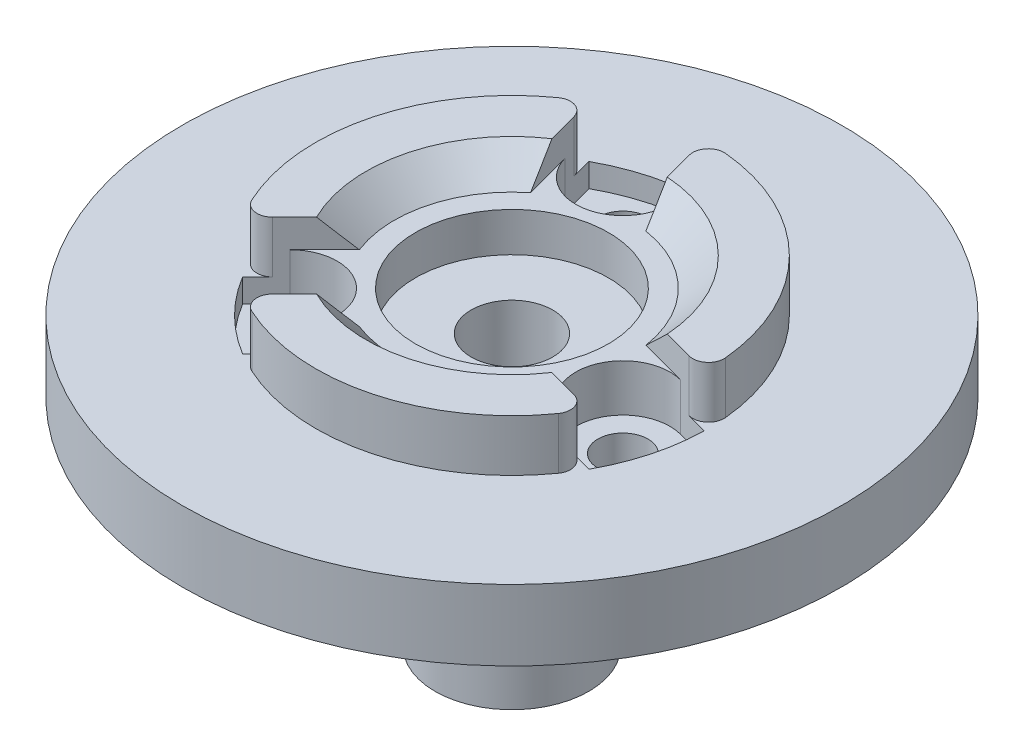
SolidWorks part; units mm, degrees
material "CA"
ref_plane "前视基准面" through (0, 0, 0) normal (0, 0, 1) x (1, 0, 0)
ref_plane "上视基准面" through (0, 0, 0) normal (0, 1, 0) x (1, 0, 0)
ref_plane "右视基准面" through (0, 0, 0) normal (1, 0, 0) x (0, 0, -1)
sketch "草图1" plane through (0, 0, 0) normal (0, 1, 0) x (1, 0, 0)
  circle A0 centre (0, 0) radius 4
  circle A1 centre (0, 0) radius 2.625
  dimension "D1" = 8
  dimension "D2" = 5.25
extrude "凸台-拉伸1" add sketch "草图1" along normal blind 6
sketch "草图2" plane through (0, 0, 0) normal (0, -1, 0) x (-1, 0, 0)
  circle A0 centre (0, 0) radius 12.5
  circle A1 centre (0, 0) radius 4 construction
  circle A2 centre (0, 0) radius 2.6
  dimension "D1" = 25
  dimension "D2" = 5.2
extrude "凸台-拉伸2" add sketch "草图2" against normal blind 6
sketch "草图3" plane through (0, 6, 0) normal (0, 1, 0) x (1, 0, 0)
  line L0 (-2.5882, 9.6593) -> (0, 0) construction
  line L1 (0, 0) -> (0, 2.7054) construction
  circle A0 centre (-2.5882, 9.6593) radius 1.6
  dimension "D1" = 3.2
  dimension "D2" = 10
  dimension "D3" = 15
extrude "切除-拉伸1" cut sketch "草图3" against normal blind 15
sketch "草图6" plane through (0, 6, 0) normal (0, 1, 0) x (1, 0, 0)
  line L0 (-6.0385, 10.9447) -> (-5.486, 8.8828)
  line L1 (0.3096, 10.4357) -> (-0.2429, 12.4976)
  line L2 (-2.5882, 9.6593) -> (0, 0) construction
  circle A0 centre (-2.5882, 9.6593) radius 1.6
  circle A1 centre (-2.5882, 9.6593) radius 3
  circle A2 centre (0, 0) radius 12.5
  circle A3 centre (0, 0) radius 12.5 construction
  circle A6 centre (-2.5882, 9.6593) radius 1.6 construction
  dimension "D1" = 3.2
  dimension "D2" = 6
extrude "切除-拉伸5" cut sketch "草图6" against normal blind 3
pattern_circular "阵列(圆周)1" count 3 over 360 about axis through (0, 0, 0) along (0, 1, 0) of "切除-拉伸1", "切除-拉伸5"
sketch "草图4" plane through (0, 0, 0) normal (0, -1, 0) x (-1, 0, 0)
  circle A0 centre (0, 0) radius 2.6
  circle A1 centre (0, 0) radius 4.9
  dimension "D1" = 9.8
  dimension "D2" = 5.2
extrude "凸台-拉伸3" add sketch "草图4" along normal blind 13.8
sketch "草图7" plane through (0, 6, 0) normal (0, 1, 0) x (1, 0, 0)
  circle A0 centre (0, 0) radius 6.15
  circle A2 centre (0, 0) radius 2.6 construction
  dimension "D1" = 12.3
extrude "切除-拉伸7" cut sketch "草图7" against normal blind 2.5
sketch "草图8" plane through (0, -13.8, 0) normal (0, -1, 0) x (-1, 0, 0)
  line L0 (0, 0) -> (-9.6593, -2.5882) construction
  line L1 (-2.572, -2.572) -> (0.9414, -3.5134)
  line L2 (0.9414, -3.5134) -> (3.5134, -0.9414)
  line L3 (3.5134, -0.9414) -> (2.572, 2.572)
  line L4 (2.572, 2.572) -> (-0.9414, 3.5134)
  line L5 (-0.9414, 3.5134) -> (-3.5134, 0.9414)
  line L6 (-3.5134, 0.9414) -> (-2.572, -2.572)
  circle A0 centre (0, 0) radius 3.15 construction
  circle A1 centre (0, 0) radius 2.6 construction
  circle A2 centre (-9.6593, -2.5882) radius 1.6 construction
  dimension "D1" = 6.3
extrude "切除-拉伸8" cut sketch "草图8" against normal blind 12.55
sketch "草图10" plane through (0, 0, 0) normal (0, 1, 0) x (1, 0, 0)
  circle A0 centre (0, 0) radius 12.5
  circle A1 centre (0, 0) radius 21
  arc A2 (12.4976, -0.2429) -> (-0.2429, 12.4976) centre (0, 0) ccw construction
  dimension "D1" = 42
extrude "凸台-拉伸4" add sketch "草图10" along normal blind 4.5
sketch "草图11" plane through (0, 6, 0) normal (0, 1, 0) x (1, 0, 0)
  line L0 (-5.2307, 7.9303) -> (-6.0385, 10.9447)
  line L1 (-6.0385, 10.9447) -> (-5.486, 8.8828) construction
  line L2 (-9.1924, -4.9497) -> (-10.7018, -6.4592) construction
  line L3 (-10.7018, -6.4592) -> (-8.4951, -4.2525)
  arc A0 (-6.0385, 10.9447) -> (-10.7018, -6.4592) centre (0, 0) ccw
  arc A1 (-5.2307, 7.9303) -> (-8.4951, -4.2525) centre (0, 0) ccw
  arc A2 (-6.0385, 10.9447) -> (-10.7018, -6.4592) centre (0, 0) ccw construction
  dimension "D1" = 3
extrude "凸台-拉伸5" add sketch "草图11" along normal blind 1.8
pattern_circular "阵列(圆周)2" count 3 over 360 about axis through (0, 3.5, 0) along (0, 1, 0) of "凸台-拉伸5"
fillet "圆角1" radius 1 6 edges at (-10.7018, 6.15, 6.4592) (-6.4592, 6.15, 10.7018) (10.9447, 6.15, 6.0385) (12.4976, 6.15, 0.2429) (-0.2429, 6.15, -12.4976) (-6.0385, 6.15, -10.9447)
chamfer "倒角1" distance 0.5 angle 45 1 edges at (0, 0, 4.9)
chamfer "倒角2" distance 2 angle 45 3 edges at (6.7175, 6, -6.7175) (2.4588, 6, 9.1763) (-9.1763, 6, -2.4588)
